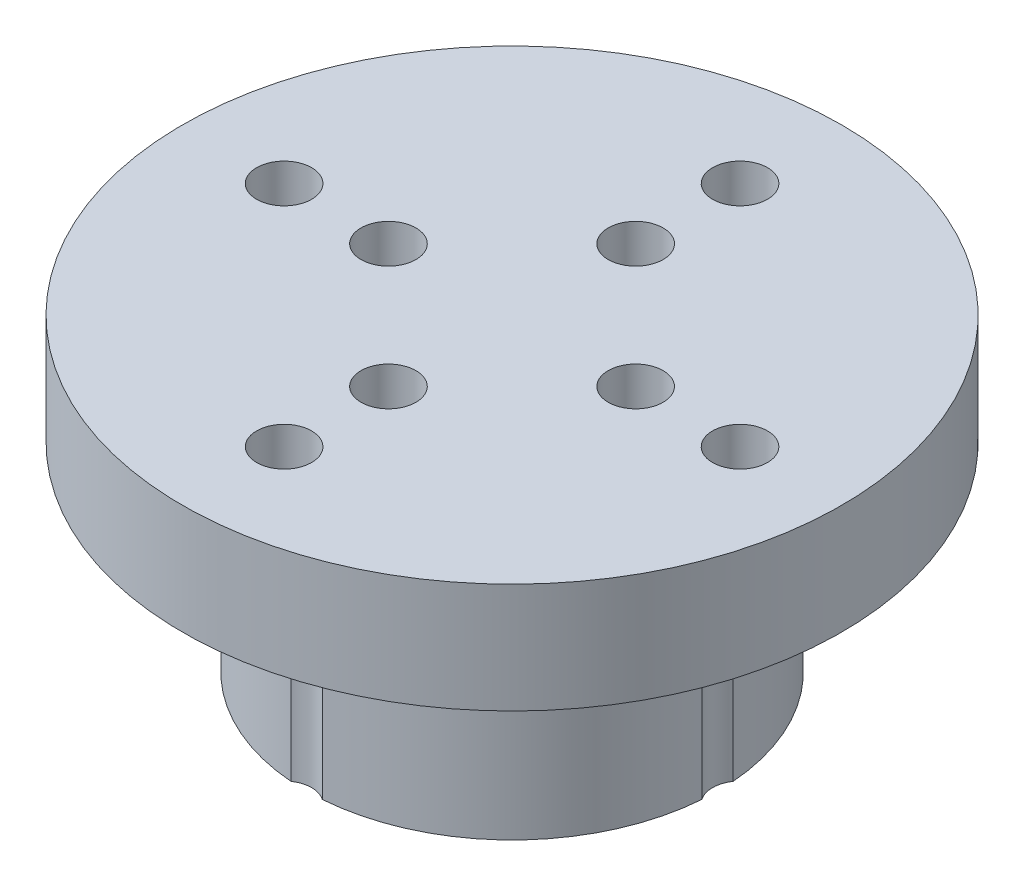
SolidWorks part; units mm, degrees
ref_plane "Front Plane" through (0, 0, 0) normal (0, 0, 1) x (1, 0, 0)
ref_plane "Top Plane" through (0, 0, 0) normal (0, 1, 0) x (1, 0, 0)
ref_plane "Right Plane" through (0, 0, 0) normal (1, 0, 0) x (0, 0, -1)
sketch "Sketch1" plane through (0, 0, 0) normal (0, 0, 1) x (1, 0, 0)
  line L0 (0, 0) -> (0, 15.6368) construction
  line L1 (0, 11.25) -> (0, 0)
  line L2 (0, 11.25) -> (12, 11.25)
  line L3 (8.5, 5.25) -> (8.5, 7.25)
  line L4 (8.5, 5.25) -> (7.5, 5.25)
  line L5 (7.5, 5.25) -> (7.5, 0)
  line L7 (8.5, 7.25) -> (12, 7.25)
  line L8 (12, 7.25) -> (12, 11.25)
  line L10 (0, 0) -> (7.5, 0)
  dimension "D1" = 7.5
  dimension "D2" = 1
  dimension "D3" = 5.25
  dimension "D4" = 2
  dimension "D5" = 12
  dimension "D6" = 4
revolve "Revolve1" add sketch "Sketch1" angle 360 about L0
sketch "Sketch2" plane through (0, 11.25, 0) normal (0, 1, 0) x (1, 0, 0)
  circle A0 centre (8.3, 0) radius 1
  circle A1 centre (4.5, 0) radius 1
  dimension "D2" = 2
  dimension "D3" = 2
  dimension "D4" = 4.5
  dimension "D1" = 8.3
extrude "Cut-Extrude1" cut sketch "Sketch2" against normal through all
pattern_circular "CirPattern1" count 4 over 360 about axis through (0, 11.25, 0) along (0, -1, 0) of "Cut-Extrude1"
